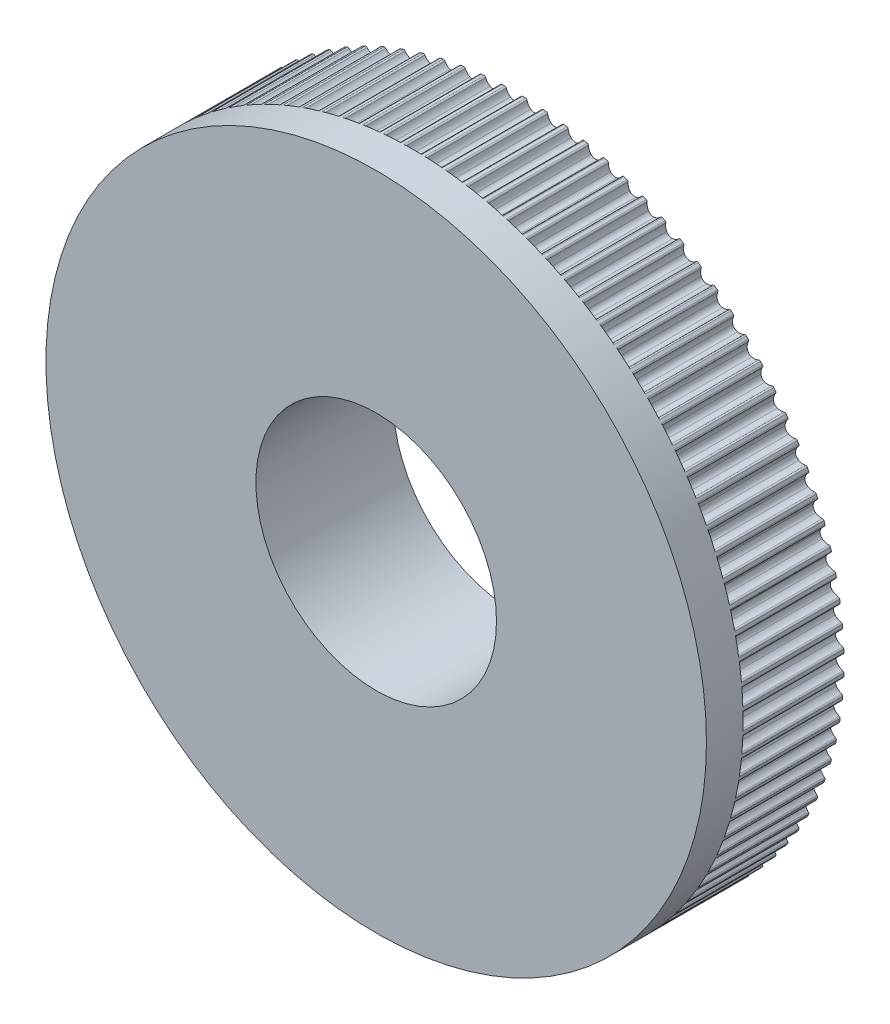
SolidWorks part; units mm, degrees
ref_plane "Front Plane" through (0, 0, 0) normal (0, 0, 1) x (1, 0, 0)
ref_plane "Top Plane" through (0, 0, 0) normal (0, 1, 0) x (1, 0, 0)
ref_plane "Right Plane" through (0, 0, 0) normal (1, 0, 0) x (0, 0, -1)
sketch "Sketch1" plane through (0, 0, 0) normal (0, 0, 1) x (1, 0, 0)
  line L3 (0, 31.5722) -> (1.999, 31.5089) construction
  line L4 (0, 0) -> (0, 30.8222) construction
  line L5 (0, 30.8222) -> (0, 32.1035) construction
  line L15 (1.999, 31.5089) -> (2.0367, 32.1035)
  line L16 (2.0367, 32.1035) -> (-2.0367, 32.1035)
  line L17 (0, 30.8222) -> (0.1538, 30.8222) construction
  line L18 (-1.999, 31.5089) -> (-2.0367, 32.1035)
  circle A0 centre (0, 0) radius 31.826 construction
  circle A1 centre (0, 0) radius 31.5722 construction
  circle A2 centre (0, 0) radius 31.3182 construction
  arc A10 (0.8511, 31.5607) -> (1.999, 31.5089) centre (0, 0) cw
  arc A11 (-0.3168, 30.9215) -> (0.3168, 30.9215) centre (0, 31.3772) ccw
  arc A12 (0.3168, 30.9215) -> (0.7035, 31.4541) centre (-0.254, 31.7426) ccw
  arc A13 (0.7035, 31.4541) -> (0.8511, 31.5607) centre (0.8471, 31.4108) cw
  arc A14 (-0.8511, 31.5607) -> (-1.999, 31.5089) centre (0, 0) ccw
  arc A15 (-0.7035, 31.4541) -> (-0.8511, 31.5607) centre (-0.8471, 31.4108) ccw
  arc A16 (-0.3168, 30.9215) -> (-0.7035, 31.4541) centre (0.254, 31.7426) cw
  point P11 (0, 31.826)
  point P13 (0, 31.5722)
  point P14 (0, 31.3182)
  dimension "D2" = 0.2775
sketch "Sketch2" plane through (0, 0, 0) normal (1, 0, 0) x (0, 0, -1)
  line L0 (-0.125, 11.5) -> (9.525, 11.5)
  line L3 (-0.125, 11.5) -> (-0.125, 31.5722)
  line L9 (9.525, 31.5722) -> (9.525, 11.5)
  line L10 (-9.525, 0) -> (9.525, 0) construction
  line L16 (-0.125, 31.5722) -> (9.525, 31.5722)
  point P25 (9.525, 0)
  point P26 (-0.125, 0)
  dimension "OA" = 19.05
  dimension "Bore" = 23
  dimension "Outside Width" = 9.65
revolve "Revolve1" add sketch "Sketch2" angle 360 mid plane about L10
sketch "Sketch3" plane through (0, 0, 0) normal (0, 0, 1) x (1, 0, 0)
  line L3 (1.999, 31.5089) -> (2.0367, 32.1035) construction
  line L4 (-1.999, 31.5089) -> (-2.0367, 32.1035) construction
  line L5 (2.0367, 32.1035) -> (-2.0367, 32.1035) construction
  line L6 (1.999, 31.5089) -> (2.0367, 32.1035)
  line L7 (-1.999, 31.5089) -> (-2.0367, 32.1035)
  line L8 (2.0367, 32.1035) -> (-2.0367, 32.1035)
  arc A0 (1.999, 31.5089) -> (0.8511, 31.5607) centre (0, 0) ccw construction
  arc A1 (0.8511, 31.5607) -> (0.7035, 31.4541) centre (0.8471, 31.4108) ccw construction
  arc A3 (0.3168, 30.9215) -> (0.7035, 31.4541) centre (-0.254, 31.7426) ccw construction
  arc A4 (-0.3168, 30.9215) -> (0.3168, 30.9215) centre (0, 31.3772) ccw construction
  arc A5 (-0.7035, 31.4541) -> (-0.3168, 30.9215) centre (0.254, 31.7426) ccw construction
  arc A6 (-0.7035, 31.4541) -> (-0.8511, 31.5607) centre (-0.8471, 31.4108) ccw construction
  arc A7 (-0.8511, 31.5607) -> (-1.999, 31.5089) centre (0, 0) ccw construction
  arc A8 (1.999, 31.5089) -> (0.8511, 31.5607) centre (0, 0) ccw
  arc A9 (0.8511, 31.5607) -> (0.7035, 31.4541) centre (0.8471, 31.4108) ccw
  arc A10 (0.3168, 30.9215) -> (0.7035, 31.4541) centre (-0.254, 31.7426) ccw
  arc A11 (-0.3168, 30.9215) -> (0.3168, 30.9215) centre (0, 31.3772) ccw
  arc A12 (-0.7035, 31.4541) -> (-0.3168, 30.9215) centre (0.254, 31.7426) ccw
  arc A13 (-0.7035, 31.4541) -> (-0.8511, 31.5607) centre (-0.8471, 31.4108) ccw
  arc A14 (-0.8511, 31.5607) -> (-1.999, 31.5089) centre (0, 0) ccw
extrude "Cut-Extrude1" cut sketch "Sketch3" against normal through all from surface starting at face at (11.5, 0, 0.125)
pattern_circular "CirPattern1" count 100 over 360 about axis through (0, 0, 9.525) along (0, 0, 1) of "Cut-Extrude1"
sketch "Sketch4"
  dimension "D1" = 4.1656
extrude "Cut-Extrude2" [suppressed] cut sketch "Sketch4" along normal through all
ref_plane "Plane1" through (0, 0, 4.825) normal (0, 0, 1) x (1, 0, 0)
sketch "Sketch5" [suppressed] plane through (0, 0, 4.825) normal (0, 0, 1) x (1, 0, 0)
  line L0 (3.3783, -2.0828) -> (18.9358, -2.0828) construction
  line L1 (4.3498, -2.0828) -> (18.5548, -2.0828)
  line L2 (18.9358, -1.7018) -> (18.9358, 0)
  line L3 (18.9358, 0) -> (3.9688, 0) construction
  line L4 (3.9688, -1.7018) -> (3.9688, 0)
  line L5 (4.3498, -2.0828) -> (3.9688, -1.7018)
  line L6 (18.5548, -2.0828) -> (18.9358, -1.7018)
  line L13 (3.3783, -2.0828) -> (18.9358, -2.0828) construction
  line L23 (3.9688, 0) -> (18.9358, 0)
  circle A0 centre (0, 0) radius 19.05 construction
  circle A1 centre (0, 0) radius 3.9688 construction
  point P0 (3.9688, -2.0828)
  point P3 (18.9358, -2.0828)
  point P4 (-19.05, 0)
  point P6 (-3.9688, 0)
revolve "Revolve2" [suppressed] add sketch "Sketch5" angle 360 mid plane about L3
sketch "Sketch6" [suppressed] plane through (18.9358, 0, 0) normal (1, 0, 0) x (0, 0, -1)
  line L1 (-4.825, 1.2025) -> (-5.8664, 0.6013)
  line L2 (-5.8664, 0.6013) -> (-5.8664, -0.6013)
  line L3 (-5.8664, -0.6013) -> (-4.825, -1.2025)
  line L4 (-4.825, -1.2025) -> (-3.7836, -0.6013)
  line L5 (-3.7836, -0.6013) -> (-3.7836, 0.6013)
  line L6 (-3.7836, 0.6013) -> (-4.825, 1.2025)
  circle A0 centre (-4.825, 0) radius 1.0414 construction
  dimension "D1" = 2.0828
extrude "Cut-Extrude3" [suppressed] cut sketch "Sketch6" against normal blind 1.524
pattern_circular "CirPattern2" [suppressed] count 2 over 90 of bodies 104
ref_axis "Center Axis 1" through (0, 0, -9.525) along (0, 0, 1)
ref_plane "Contact Plane 2" through (0, 0, -9.525) normal (0, 0, -1) x (-1, 0, 0)
sketch "Sketch7" plane through (0, 0, 0.125) normal (0, 0, 1) x (1, 0, 0)
  circle A0 centre (0, 0) radius 31.5722
  circle A1 centre (0, 0) radius 11.5
extrude "Boss-Extrude1" add sketch "Sketch7" along normal blind 3.5
equation "\"D2@Sketch1\" = \"R3@Sketch1\"/2"
equation "\"D1@Sketch6\" = \"D1@Sketch4\"/2"
